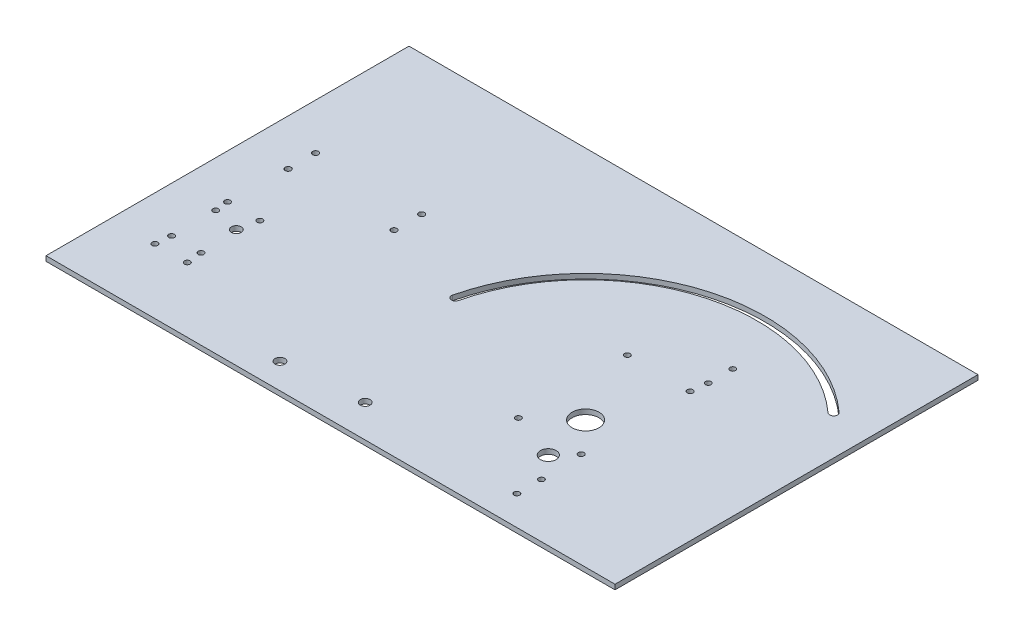
SolidWorks part; units mm, degrees
ref_plane "Front Plane" through (0, 0, 0) normal (0, 0, 1) x (1, 0, 0)
ref_plane "Top Plane" through (0, 0, 0) normal (0, 1, 0) x (1, 0, 0)
ref_plane "Right Plane" through (0, 0, 0) normal (1, 0, 0) x (0, 0, -1)
sketch "Sketch1" plane through (0, 0, 0) normal (0, 1, 0) x (1, 0, 0)
  line L1 (-158.75, 88.9) -> (158.75, 88.9)
  line L2 (-158.75, 88.9) -> (-158.75, -88.9)
  line L3 (-158.75, -88.9) -> (158.75, -88.9)
  line L4 (158.75, 88.9) -> (158.75, -88.9)
  line L5 (-158.75, 88.9) -> (158.75, -88.9) construction
  line L6 (-158.75, -88.9) -> (158.75, 88.9) construction
  circle A0 centre (-111.76, -12.7) radius 3.175
  circle A1 centre (107.95, -6.35) radius 8.7313
  circle A4 centre (-129.032, 55.88) radius 1.905
  circle A5 centre (-60.452, 55.88) radius 1.905
  circle A7 centre (-129.032, 38.1) radius 1.905
  circle A8 centre (-60.452, 38.1) radius 1.905
  point P0 (0, 0)
  dimension "D3" = 6.35
  dimension "D4" = 17.4625
  dimension "D14" = 3.81
  dimension "D17" = 17.78
  dimension "D1" = 317.5
  dimension "D2" = 177.8
  dimension "D5" = 46.99
  dimension "D6" = 266.7
  dimension "D7" = 95.25
  dimension "D8" = 76.2
  dimension "D13" = 29.718
  dimension "D15" = 68.58
  dimension "D16" = 127
extrude "Boss-Extrude1" add sketch "Sketch1" along normal blind 3.175
sketch "Sketch2" plane through (0, 3.175, 0) normal (0, 1, 0) x (1, 0, 0)
  line L0 (-158.75, 88.9) -> (-158.75, -88.9) construction
  line L1 (-158.75, -88.9) -> (158.75, -88.9) construction
  circle A0 centre (-89.0817, -33.177) radius 1.905
  circle A1 centre (-132.1376, -36.4483) radius 1.905
  dimension "D1" = 3.81
  dimension "D2" = 69.6683
  dimension "D3" = 52.4517
  dimension "D4" = 55.723
  dimension "D5" = 43.18
extrude "Cut-Extrude1" [suppressed] cut sketch "Sketch2" against normal through all
sketch "Sketch3" plane through (0, 0, 0) normal (0, -1, 0) x (-1, 0, 0)
  line L0 (158.75, -88.9) -> (-158.75, -88.9) construction
  line L1 (158.75, 88.9) -> (158.75, -88.9) construction
  circle A0 centre (23.8295, -72.39) radius 3.175
  circle A1 centre (-26.7643, -67.818) radius 3.175
  dimension "D1" = 6.35
  dimension "D2" = 4.572
  dimension "D3" = 16.51
  dimension "D4" = 185.5143
  dimension "D5" = 50.8
extrude "Cut-Extrude2" cut sketch "Sketch3" against normal through all
sketch "Sketch4" plane through (0, 3.175, 0) normal (0, 1, 0) x (1, 0, 0)
  line L0 (-158.75, -88.9) -> (158.75, -88.9) construction
  line L1 (158.75, 88.9) -> (133.35, 88.9)
  line L2 (158.75, 88.9) -> (158.75, -88.9)
  line L3 (158.75, -88.9) -> (133.35, -88.9)
  line L4 (133.35, 88.9) -> (133.35, -88.9)
  dimension "D1" = 25.4
extrude "Cut-Extrude3" cut sketch "Sketch4" against normal through all
sketch "Sketch5" plane through (0, 3.175, 0) normal (0, 1, 0) x (1, 0, 0)
  line L0 (133.35, 88.9) -> (-158.75, 88.9) construction
  line L1 (133.35, 88.9) -> (133.35, -88.9) construction
  circle A0 centre (115.57, -38.1) radius 5.08
  dimension "D3" = 10.16
  dimension "D1" = 127
  dimension "D2" = 17.78
extrude "Cut-Extrude4" cut sketch "Sketch5" against normal through all
sketch "Sketch6" plane through (0, 0, 0) normal (0, -1, 0) x (1, 0, 0)
  line L0 (-158.75, 88.9) -> (133.35, 88.9) construction
  line L1 (133.35, -88.9) -> (133.35, 88.9) construction
  line L2 (133.35, -88.9) -> (-158.75, -88.9) construction
  circle A0 centre (127, 69.85) radius 1.8034
  circle A2 centre (127, 53.975) radius 1.8034
  circle A3 centre (127, -53.975) radius 1.8034
  circle A4 centre (127, -69.85) radius 1.8034
  dimension "D4" = 3.6068
  dimension "D5" = 6.35
  dimension "D1" = 15.875
  dimension "D2" = 19.05
  dimension "D3" = 6.35
  dimension "D6" = 15.875
  dimension "D7" = 19.05
extrude "Cut-Extrude5" cut sketch "Sketch6" against normal through all
sketch "Sketch7" plane through (0, 3.175, 0) normal (0, 1, 0) x (1, 0, 0)
  line L0 (133.35, 88.9) -> (133.35, -88.9) construction
  line L1 (133.35, 88.9) -> (-158.75, 88.9) construction
  line L2 (-158.75, 88.9) -> (-158.75, -88.9) construction
  line L3 (-158.75, -88.9) -> (133.35, -88.9) construction
  circle A1 centre (125.73, 43.4975) radius 1.8415
  circle A2 centre (85.09, 43.4975) radius 1.8415
  circle A3 centre (85.09, -26.9875) radius 1.8415
  circle A4 centre (125.73, -26.9875) radius 1.8415
  circle A5 centre (-130.175, -46.99) radius 1.8415
  circle A6 centre (-109.22, -46.99) radius 1.8415
  circle A7 centre (-129.2225, -37.1475) radius 1.8415
  circle A8 centre (-110.1725, -37.1475) radius 1.8415
  circle A9 centre (-129.2225, -8.5725) radius 1.8415
  circle A10 centre (-130.175, 0) radius 1.8415
  circle A11 centre (-109.22, 0) radius 1.8415
  dimension "D1" = 7.62
  dimension "D5" = 3.683
  dimension "D10" = 3.683
  dimension "D15" = 3.683
  dimension "D2" = 40.64
  dimension "D3" = 70.485
  dimension "D4" = 61.9125
  dimension "D6" = 28.575
  dimension "D7" = 20.955
  dimension "D8" = 0.9525
  dimension "D9" = 19.05
  dimension "D11" = 88.9
  dimension "D12" = 8.5725
  dimension "D13" = 28.575
  dimension "D14" = 9.8425
extrude "Cut-Extrude6" cut sketch "Sketch7" against normal through all
sketch "Sketch8" plane through (0, 0, 0) normal (0, -1, 0) x (1, 0, 0)
  line L1 (-158.75, -88.9) -> (-158.75, 88.9) construction
  line L2 (-158.75, 88.9) -> (133.35, 88.9) construction
  line L3 (133.35, 88.9) -> (133.35, -88.9)
  line L4 (133.35, -88.9) -> (-158.75, -88.9) construction
  line L5 (133.35, -88.9) -> (-158.75, -88.9)
  line L6 (-158.75, -88.9) -> (-158.75, -146.05)
  line L7 (-158.75, -146.05) -> (209.55, -146.05)
  line L8 (209.55, -146.05) -> (209.55, 88.9)
  line L9 (209.55, 88.9) -> (133.35, 88.9)
  line L12 (133.35, -88.9) -> (133.35, 88.9) construction
  dimension "D1" = 76.2
  dimension "D2" = 57.15
extrude "Boss-Extrude2" add sketch "Sketch8" against normal through all
sketch "Sketch9" plane through (0, 0, 0) normal (0, -1, 0) x (1, 0, 0)
  line L2 (209.55, -146.05) -> (209.55, 88.9) construction
  arc A0 (185.8528, -79.875) -> (182.4472, -76.1056) centre (184.15, -77.9903) ccw
  arc A1 (-0.15, -19.402) -> (-5.0917, -20.5792) centre (-2.6208, -19.9906) ccw
  circle A2 centre (107.95, 6.35) radius 113.665 construction
  arc A3 (182.4472, -76.1056) -> (-0.15, -19.402) centre (107.95, 6.35) cw
  arc A4 (185.8528, -79.875) -> (-5.0917, -20.5792) centre (107.95, 6.35) cw
  arc A5 (-5.0917, -20.5792) -> (-2.0046, -22.4547) centre (-2.6208, -19.9906) ccw construction
  arc A6 (-2.0046, -22.4547) -> (-0.15, -19.402) centre (-2.6208, -19.9906) ccw construction
  arc A7 (182.2464, -79.672) -> (185.8528, -79.875) centre (184.15, -77.9903) ccw construction
  arc A8 (182.4472, -76.1056) -> (182.2464, -79.672) centre (184.15, -77.9903) ccw construction
  circle A12 centre (107.95, 6.35) radius 8.7313 construction
  point P1 (0, 0)
  point P3 (0, 0)
  point P4 (0, 0)
  point P14 (0, 0)
  point P16 (0, 0)
  point P19 (0, 0)
  point P21 (0, 0)
  point P22 (0, 0)
  point P23 (0, 0)
  dimension "D1" = 5.08
  dimension "D6" = 227.33
  dimension "D2" = 25.4
  dimension "D5" = 186.7708
extrude "Cut-Extrude7" cut sketch "Sketch9" against normal through all
